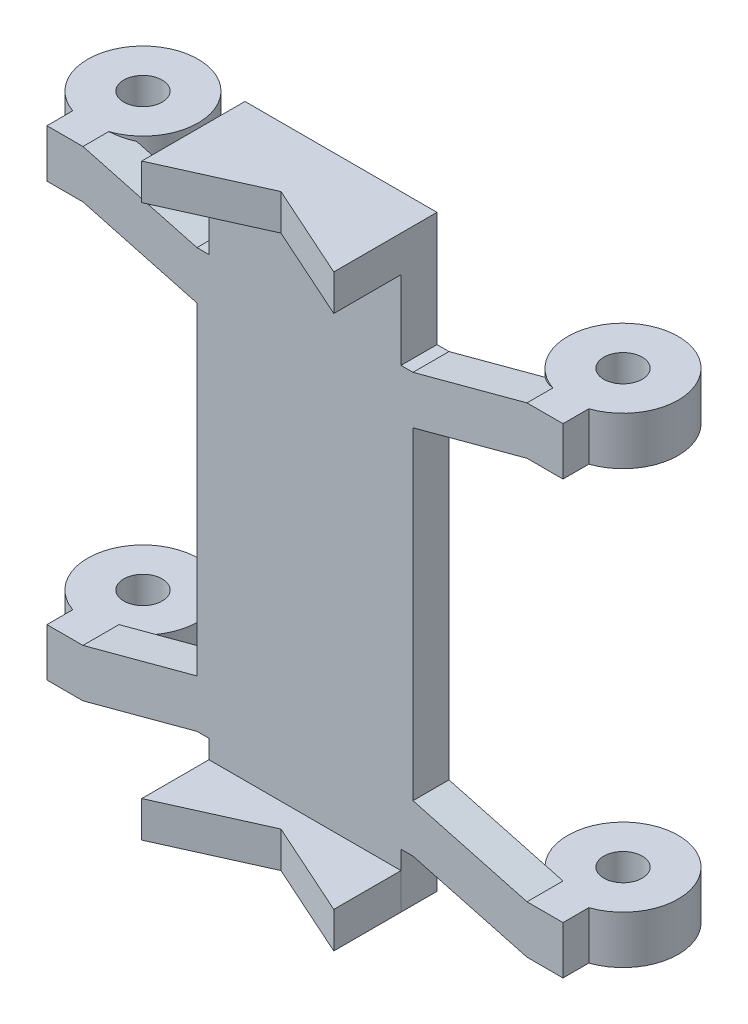
SolidWorks part; units mm, degrees
ref_plane "Front Plane" through (0, 0, 0) normal (0, 0, 1) x (1, 0, 0)
ref_plane "Top Plane" through (0, 0, 0) normal (0, 1, 0) x (1, 0, 0)
ref_plane "Right Plane" through (0, 0, 0) normal (1, 0, 0) x (0, 0, -1)
sketch "Sketch1" plane through (0, 0, 0) normal (0, 1, 0) x (1, 0, 0)
  line L0 (0, -55) -> (0, 55) construction
  circle A0 centre (-20, 0) radius 1.6
  circle A1 centre (20, 0) radius 1.6
  dimension "D1" = 3.2
  dimension "D2" = 40
sketch "Sketch2" plane through (0, 0, 0) normal (0, 1, 0) x (1, 0, 0)
  circle A0 centre (20, 0) radius 1.6 construction
  circle A1 centre (-20, 0) radius 1.6 construction
  circle A2 centre (20, 0) radius 1.6
  circle A3 centre (-20, 0) radius 1.6
  circle A4 centre (-20, 0) radius 4.6
  circle A5 centre (20, 0) radius 4.6
  dimension "D1" = 3
extrude "Boss-Extrude1" add sketch "Sketch2" along normal blind 4
sketch "Sketch3" plane through (0, 0, 0) normal (0, 0, 1) x (1, 0, 0)
  line L1 (-20, 0) -> (20, 0)
  line L2 (-20, 0) -> (-20, 40)
  line L3 (-20, 40) -> (20, 40)
  line L4 (20, 0) -> (20, 40)
  point P5 (0, 0)
  dimension "D1" = 40
pattern_linear "LPattern1" count 2 spacing 36 along (0, 1, 0) of "Boss-Extrude1"
sketch "Sketch4" plane through (0, 0, 0) normal (0, 0, 1) x (1, 0, 0)
  line L0 (-15.4, 0) -> (-9, 5)
  line L1 (-24.6, 0) -> (-15.4, 0) construction
  line L2 (-15.4, 0) -> (-18.4, 0)
  line L4 (-15.4, 4) -> (-24.6, 4) construction
  line L5 (-15.4, 4) -> (-9, 9)
  line L6 (0, -55) -> (0, 55) construction
  line L12 (-24.6, 36) -> (-15.4, 36) construction
  line L13 (-43.6748, 20) -> (12.0601, 20) construction
  line L22 (-9, 31) -> (-9, 9)
  line L23 (-9, 5) -> (9, 5)
  line L24 (9, 9) -> (9, 31)
  line L25 (9, 35) -> (-9, 35)
  line L26 (-18.4, 0) -> (-21.6, 0) construction
  line L27 (-18.4, 0) -> (-21.6, 0) construction
  line L28 (-15.4, 4) -> (-18.4, 4)
  line L29 (-18.4, 4) -> (-18.4, 0)
  line L30 (18.4, 4) -> (18.4, 0)
  line L31 (15.4, 4) -> (18.4, 4)
  line L32 (15.4, 4) -> (9, 9)
  line L33 (15.4, 0) -> (18.4, 0)
  line L34 (15.4, 0) -> (9, 5)
  line L35 (-15.4, 36) -> (-9, 31)
  line L36 (-15.4, 40) -> (-9, 35)
  line L37 (-18.4, 36) -> (-18.4, 40)
  line L38 (-15.4, 36) -> (-18.4, 36)
  line L39 (-15.4, 40) -> (-18.4, 40)
  line L40 (15.4, 40) -> (9, 35)
  line L41 (15.4, 40) -> (18.4, 40)
  line L42 (15.4, 36) -> (9, 31)
  line L43 (15.4, 36) -> (18.4, 36)
  line L44 (18.4, 36) -> (18.4, 40)
  dimension "D1" = 18
  dimension "D2" = 22
extrude "Boss-Extrude2" [suppressed] add sketch "Sketch4" along normal mid plane 3
ref_plane "Plane1" through (0, 0, 3.5) normal (0, 0, 1) x (1, 0, 0)
sketch "Sketch7" plane through (0, 0, 3.5) normal (0, 0, 1) x (1, 0, 0)
  line L0 (-21.5, 0) -> (-21.5, 4)
  line L1 (-21.5, 4) -> (-18.5, 4)
  line L3 (-18.5, 0) -> (-21.5, 0)
  line L5 (-15.4, 4) -> (-24.6, 4) construction
  line L6 (-18.5, 4) -> (-9, 6.5455)
  line L7 (-18.5, 0) -> (-9, 2.5455)
  line L8 (-47.7161, 20) -> (-2.7379, 20) construction
  line L9 (-24.6, 36) -> (-15.4, 36) construction
  line L10 (0, -55) -> (0, 55) construction
  line L11 (18.5, 0) -> (9, 2.5455)
  line L12 (18.5, 4) -> (9, 6.5455)
  line L13 (18.5, 0) -> (21.5, 0)
  line L14 (21.5, 4) -> (18.5, 4)
  line L15 (21.5, 0) -> (21.5, 4)
  line L16 (21.5, 40) -> (21.5, 36)
  line L17 (21.5, 36) -> (18.5, 36)
  line L18 (18.5, 40) -> (21.5, 40)
  line L19 (18.5, 36) -> (9, 33.4545)
  line L20 (18.5, 40) -> (9, 37.4545)
  line L21 (-18.5, 40) -> (-9, 37.4545)
  line L22 (-18.5, 36) -> (-9, 33.4545)
  line L23 (-18.5, 40) -> (-21.5, 40)
  line L24 (-21.5, 36) -> (-18.5, 36)
  line L25 (-21.5, 40) -> (-21.5, 36)
  line L26 (-9, 2.5455) -> (9, 2.5455)
  line L27 (9, 6.5455) -> (9, 33.4545)
  line L28 (9, 37.4545) -> (-9, 37.4545)
  line L29 (-9, 33.4545) -> (-9, 6.5455)
  point P2 (-20, 0)
  dimension "D1" = 3
  dimension "D2" = 18
  dimension "D3" = 15
extrude "Boss-Extrude5" add sketch "Sketch7" along normal blind 3
sketch "b.e. spring plate" plane through (0, 0, 0) normal (0, 1, 0) x (1, 0, 0)
  line L0 (-3.3, 0) -> (-3.3, -3.5)
  line L1 (9, -3.5) -> (-9, -3.5) construction
  line L2 (-3.3, -3.5) -> (3.3, -3.5)
  line L3 (3.3, -3.5) -> (3.3, 0)
  circle A0 centre (0, 0) radius 1.7
  arc A2 (3.3, 0) -> (-3.3, 0) centre (0, 0) ccw
  circle A3 centre (0, 0) radius 3.3 construction
  dimension "D1" = 3.4
  dimension "D2" = 1.6
sketch "front spring plate" plane through (0, 0, 0) normal (0, 0, 1) x (1, 0, 0)
  line L1 (3.3, 7.2) -> (-3.3, 7.2)
  line L2 (3.3, 7.2) -> (3.3, 4.8)
  line L3 (3.3, 4.8) -> (-3.3, 4.8)
  line L4 (-3.3, 7.2) -> (-3.3, 4.8)
  point P4 (0, 4.8)
  dimension "D1" = 2.4
  dimension "D2" = 6.6
  dimension "D3" = 7.2
extrude "Boss-Extrude6" add sketch "b.e. spring plate" along normal up to vertex (7.2 mm away) from vertex up to point (-3.3, 7.2, 0) starting at point (3.3, 4.8, 0)
sketch "pen holder side" plane through (0, 0, 6.5) normal (0, 0, 1) x (1, 0, 0)
  line L0 (-8, 47) -> (8, 47)
  line L1 (-8, 1) -> (8, 1)
  line L2 (-8, 1) -> (-8, -2)
  line L3 (-8, -2) -> (8, -2)
  line L4 (8, 1) -> (8, -2)
  line L5 (-200125.406, -26.4432) -> (199957.0156, -26.4432)
  line L6 (-8, 47) -> (-8, 44)
  line L7 (-8, 44) -> (8, 44)
  line L8 (8, 47) -> (8, 44)
  point P4 (0, 1)
  point P13 (0, 44)
  dimension "D1" = 3
  dimension "D2" = 16
  dimension "D3" = 2
  dimension "D4" = 46
sketch "Sketch10" plane through (0, 0, 6.5) normal (0, 0, 1) x (1, 0, 0)
  line L0 (-8, -2) -> (-8, 47)
  line L1 (-8, 47) -> (8, 47)
  line L2 (8, 47) -> (8, -2)
  line L3 (8, -2) -> (-8, -2)
extrude "Boss-Extrude8" add sketch "Sketch10" against normal up to surface (3 mm away) up to face at (0, 20, 3.5)
sketch "b.e. pen holder" plane through (0, 0, 0) normal (0, 1, 0) x (1, 0, 0)
  line L0 (-8, -6.5) -> (-8, -12.1)
  line L1 (-8, -12.1) -> (0, -8.5)
  line L2 (0, -8.5) -> (8, -12.1)
  line L3 (8, -12.1) -> (8, -6.5)
  line L4 (8, -6.5) -> (-8, -6.5)
  point P2 (0, -6.5)
  dimension "D1" = 2
  dimension "D2" = 5.6
extrude "Boss-Extrude7" add sketch "b.e. pen holder" along normal up to vertex (1 mm away) from vertex separate body contours L1 L2 L3 L4 L0 up to point (-8, 1, 6.5) starting at point (-8, -2, 6.5)
extrude "Boss-Extrude9" add sketch "b.e. pen holder<3>" along normal up to vertex (47 mm away) from vertex up to point (-8, 47, 6.5) starting at point (8, 44, 6.5)
sketch "b.e. pen holder<3>" plane through (0, 0, 0) normal (0, 1, 0) x (1, 0, 0) same geometry as "b.e. pen holder"
